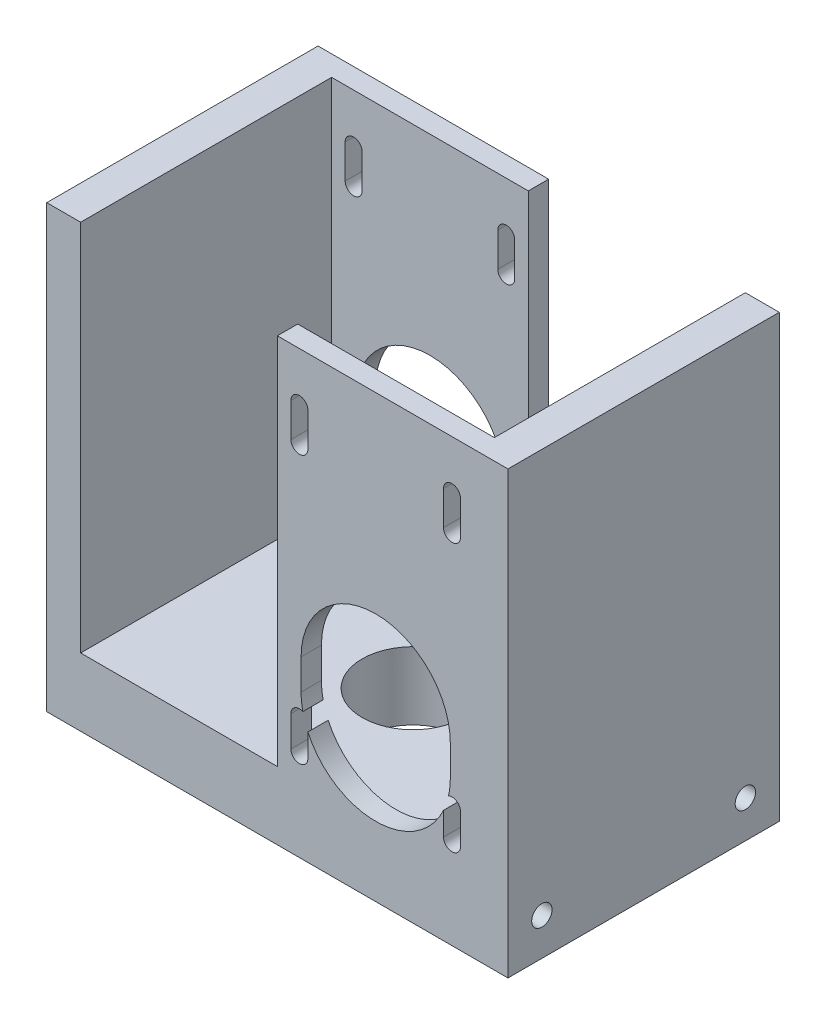
SolidWorks part; units mm, degrees
ref_plane "Front Plane" through (0, 0, 0) normal (0, 0, 1) x (1, 0, 0)
ref_plane "Top Plane" through (0, 0, 0) normal (0, 1, 0) x (1, 0, 0)
ref_plane "Right Plane" through (0, 0, 0) normal (1, 0, 0) x (0, 0, -1)
sketch "Sketch1" plane through (0, 0, 0) normal (0, 0, 1) x (1, 0, 0)
  line L1 (-34, -5) -> (34, -5)
  line L2 (-34, -5) -> (-34, 5)
  line L3 (-34, 5) -> (34, 5)
  line L4 (34, -5) -> (34, 5)
  line L5 (-34, -5) -> (34, 5) construction
  line L6 (-34, 5) -> (34, -5) construction
  line L7 (-34, 5) -> (-29, 5)
  line L8 (-34, 5) -> (-34, 60)
  line L9 (-34, 60) -> (-29, 60)
  line L10 (-29, 5) -> (-29, 60)
  line L11 (34, 5) -> (29, 5)
  line L12 (34, 5) -> (34, 60)
  line L13 (34, 60) -> (29, 60)
  line L14 (29, 5) -> (29, 60)
  point P0 (0, 0)
  dimension "D1" = 68
  dimension "D2" = 10
  dimension "D3" = 55
  dimension "D4" = 55
  dimension "D5" = 5
  dimension "D6" = 5
extrude "Boss-Extrude1" add sketch "Sketch1" along normal blind 20 and the other way blind 20 contours L3 L10 L9 L8 | L1 L4 L3 L2 | L14 L3 L12 L13 region at (0, 0, 0) region at (-31.5, 32.5, 0) region at (31.5, 32.5, 0)
sketch "Sketch2" plane through (0, 5, 0) normal (0, 1, 0) x (1, 0, 0)
  line L1 (29, -20) -> (0, -20)
  line L2 (29, -20) -> (29, -17)
  line L3 (29, -17) -> (0, -17)
  line L4 (0, -20) -> (0, -17)
  line L5 (-29, 20) -> (0, 20)
  line L6 (-29, 20) -> (-29, 17)
  line L7 (-29, 17) -> (0, 17)
  line L8 (0, 20) -> (0, 17)
  dimension "D1" = 3
  dimension "D2" = 3
extrude "Boss-Extrude2" add sketch "Sketch2" along normal blind 55
sketch "Sketch4" plane through (0, 5, 0) normal (0, 1, 0) x (1, 0, 0)
  circle A0 centre (0, 0) radius 7.5
  dimension "D1" = 15
extrude "Cut-Extrude2" cut sketch "Sketch4" against normal blind 12
sketch "Sketch5" plane through (34, 0, 0) normal (1, 0, 0) x (0, 0, -1)
  line L0 (20, -5) -> (-20, -5) construction
  line L1 (-20, -5) -> (-20, 60) construction
  line L2 (20, -5) -> (20, 60) construction
  circle A0 centre (-15, 0.5) radius 1.5
  circle A1 centre (15, 0.5) radius 1.5
  dimension "D5" = 3
  dimension "D6" = 3
  dimension "D1" = 5.5
  dimension "D2" = 5
  dimension "D3" = 5
  dimension "D4" = 5.5
extrude "Cut-Extrude3" cut sketch "Sketch5" against normal through all
sketch "Sketch3" plane through (0, 0, -20) normal (0, 0, -1) x (-1, 0, 0)
  line L0 (-29, 5) -> (0, 5) construction
  line L2 (29, 5) -> (0, 5) construction
  line L3 (29, 5) -> (29, 60) construction
  line L4 (29, 5) -> (0, 5) construction
  line L6 (0, 60) -> (0, 5) construction
  line L7 (0, 60) -> (0, 5) construction
  line L9 (2, 12.75) -> (4.5, 12.75)
  line L10 (2, 12.75) -> (2, 8.25)
  line L11 (2, 8.25) -> (4.5, 8.25)
  line L12 (4.5, 12.75) -> (4.5, 8.25)
  line L13 (24.5, 12.75) -> (27, 12.75)
  line L14 (24.5, 12.75) -> (24.5, 8.25)
  line L15 (24.5, 8.25) -> (27, 8.25)
  line L16 (27, 12.75) -> (27, 8.25)
  line L17 (3.5, 20.75) -> (25.5, 20.75)
  line L18 (3.5, 20.75) -> (3.5, 16.25)
  line L19 (3.5, 16.25) -> (25.5, 16.25)
  line L20 (25.5, 20.75) -> (25.5, 16.25)
  line L21 (2, 52.75) -> (4.5, 52.75)
  line L22 (2, 52.75) -> (2, 47.75)
  line L23 (2, 47.75) -> (4.5, 47.75)
  line L24 (4.5, 52.75) -> (4.5, 47.75)
  line L25 (24.5, 52.75) -> (27, 52.75)
  line L26 (24.5, 52.75) -> (24.5, 47.75)
  line L27 (24.5, 47.75) -> (27, 47.75)
  line L28 (27, 52.75) -> (27, 47.75)
  circle A0 centre (14.5, 16.25) radius 11
  circle A1 centre (25.75, 8.25) radius 1.25
  circle A2 centre (3.25, 8.25) radius 1.25
  circle A3 centre (3.25, 52.75) radius 1.25
  circle A4 centre (25.75, 52.75) radius 1.25
  circle A10 centre (14.5, 20.75) radius 11
  circle A11 centre (3.25, 12.75) radius 1.25
  circle A12 centre (25.75, 12.75) radius 1.25
  circle A13 centre (3.25, 47.75) radius 1.25
  circle A14 centre (25.75, 47.75) radius 1.25
  point P8 (14.5, 5)
  dimension "D1" = 22
  dimension "D12" = 2.5
  dimension "D13" = 2.5
  dimension "D14" = 2.5
  dimension "D15" = 2.5
  dimension "D16" = 2
  dimension "D17" = 2
  dimension "D18" = 40
  dimension "D2" = 11.25
  dimension "D3" = 0
  dimension "D4" = 3.25
  dimension "D5" = 3.25
  dimension "D6" = 3.25
  dimension "D7" = 3.25
  dimension "D8" = 3.25
  dimension "D10" = 3.25
  dimension "D11" = 40
extrude "Cut-Extrude1" cut sketch "Sketch3" against normal blind 63 contours A12 A0 L19 A10 A11 L12 L14 | L19 A10 | A0 A10 L19 L17 | L17 A0 | L17 A10 A0 | A11 L10 A2 L12 A0 | L11 A2 | L11 A2 | L9 A11 A0 | A11 A0 L12 | A0 A11 L9 | L9 A11 A0 | A0 A11 L9 | L15 A1 | L15 A1 | A12 A0 L14 A1 L16 | A0 A12 L13 | L13 A12 A0 | A0 A12 L13 | L13 A12 A0 | A12 L14 A0 | A10 L19 A0 | A10 A0 L20 | A0 A10 L17 | A10 A0 L19 | A10 L18 A0 | L17 A10 A0 | L21 A3 | L21 A3 | A13 L24 A3 L22 | L23 A13 | L23 A13 | L27 A14 | L27 A14 | A14 L28 A4 L26 | L25 A4 | L25 A4 region at (-3.0529, 13.2905, -20) region at (-3.2349, 10.4797, -20) region at (-3.1739, 12.1983, -20) region at (-4.14, 13.2355, -20) region at (-4.3109, 12.5151, -20) region at (-3.25, 8.7805, -20) region at (-3.25, 7.7195, -20) region at (-14.5, 9.5915, -20) region at (-4.4414, 12.1015, -20) region at (-3.8568, 16.9965, -20) region at (-3.5696, 18.5, -20) region at (-14.5, 27.3606, -20) region at (-3.8568, 20.0035, -20) region at (-14.5, 18.5, -20) region at (-14.5, 13.5703, -20) region at (-25.7651, 10.4797, -20) region at (-24.5586, 12.1015, -20) region at (-14.5, 23.4297, -20) region at (-25.1432, 20.0035, -20) region at (-25.4304, 18.5, -20) region at (-25.1432, 16.9965, -20) region at (-24.86, 13.2355, -20) region at (-24.6891, 12.5151, -20) region at (-25.75, 8.7805, -20) region at (-25.75, 7.7195, -20) region at (-25.8261, 12.1983, -20) region at (-25.9471, 13.2905, -20) region at (-3.25, 53.2805, -20) region at (-3.25, 50.25, -20) region at (-3.25, 52.2195, -20) region at (-3.25, 48.2805, -20) region at (-3.25, 47.2195, -20) region at (-25.75, 53.2805, -20) region at (-25.75, 50.25, -20) region at (-25.75, 52.2195, -20) region at (-25.75, 48.2805, -20) region at (-25.75, 47.2195, -20)
mirror "Mirror4" about plane through (0, 0, 0) normal (1, 0, 0) of "Cut-Extrude1"
